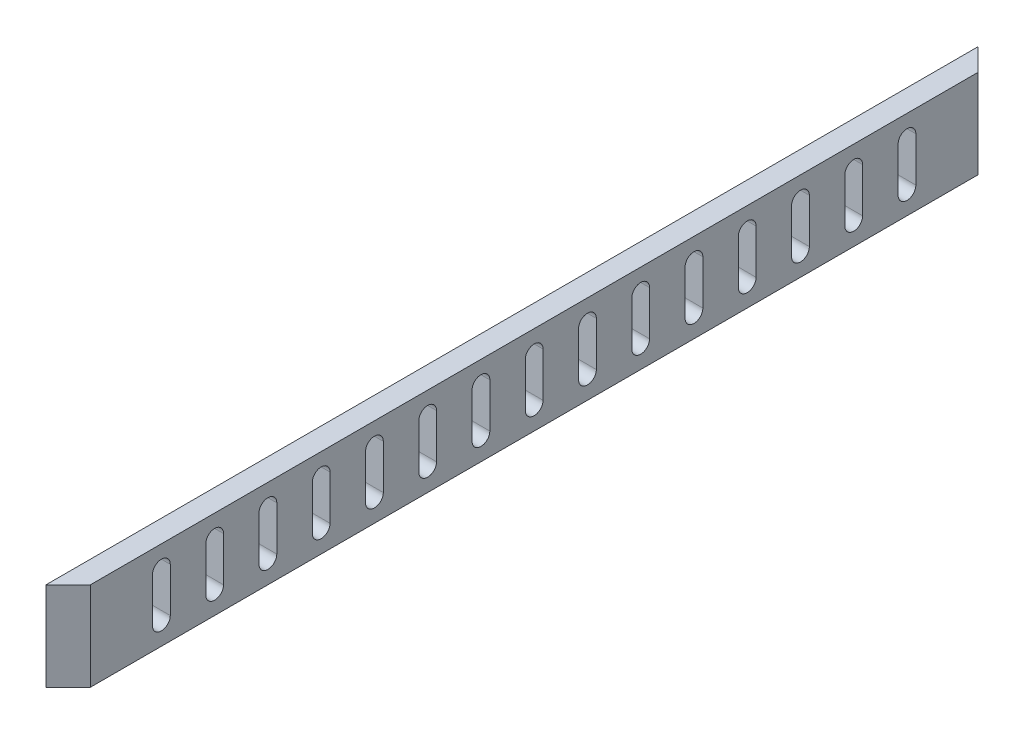
SolidWorks part; units mm, degrees
ref_plane "Plan de face" through (0, 0, 0) normal (0, 0, 1) x (1, 0, 0)
ref_plane "Plan de dessus" through (0, 0, 0) normal (0, 1, 0) x (1, 0, 0)
ref_plane "Plan de droite" through (0, 0, 0) normal (1, 0, 0) x (0, 0, -1)
sketch "Esquisse1" plane through (0, 0, 0) normal (0, 0, 1) x (1, 0, 0)
  line L0 (-10, 40) -> (-10, 0)
  line L3 (-10, 0) -> (0, 0)
  line L4 (0, 0) -> (0, 40)
  line L5 (0, 40) -> (-10, 40)
  point P2 (-6.8987, 0)
  dimension "D3" = 10
  dimension "D4" = 40
extrude "Boss.-Extru.1" add sketch "Esquisse1" along normal mid plane 600
sketch "Esquisse2" plane through (0, 0, 0) normal (0, -1, 0) x (1, 0, 0)
  line L0 (0, 200) -> (-10, 210)
  line L3 (-10, 210) -> (-10, 300)
  line L4 (-10, 300) -> (0, 300)
  line L5 (0, 300) -> (0, 200)
  line L6 (0, 300) -> (0, -300) construction
  line L7 (-10, 300) -> (-10, -300) construction
  point P2 (0, 0)
  point P4 (0, 0)
  point P6 (0, 200)
  point P17 (21.0444, 178.9556)
  dimension "D1" = 200
  dimension "D2" = 45
extrude "Enlèv. mat.-Extru.1" cut sketch "Esquisse2" against normal through all both and the other way through all
mirror "Symétrie1" about plane through (0, 0, 0) normal (0, 0, 1) of "Enlèv. mat.-Extru.1"
sketch "Esquisse3" plane through (0, 0, 0) normal (1, 0, 0) x (0, 0, -1)
  line L0 (0, 10) -> (0, 30) construction
  line L5 (-4, 10) -> (-4, 30)
  line L6 (4, 10) -> (4, 30)
  line L7 (-200, 40) -> (200, 40) construction
  line L10 (-200, 0) -> (200, 0) construction
  arc A0 (-4, 10) -> (4, 10) centre (0, 10) ccw
  arc A1 (4, 30) -> (-4, 30) centre (0, 30) ccw
  point P2 (0, 20)
  dimension "D1" = 4
  dimension "D2" = 10
  dimension "D3" = 10
extrude "Enlèv. mat.-Extru.2" cut sketch "Esquisse3" against normal through all both and the other way through all
pattern_linear "Répétition linéaire1" count 8 spacing 24 along (0, 0, 1) count 8 spacing 24 along (0, 0, -1) of "Enlèv. mat.-Extru.2"
